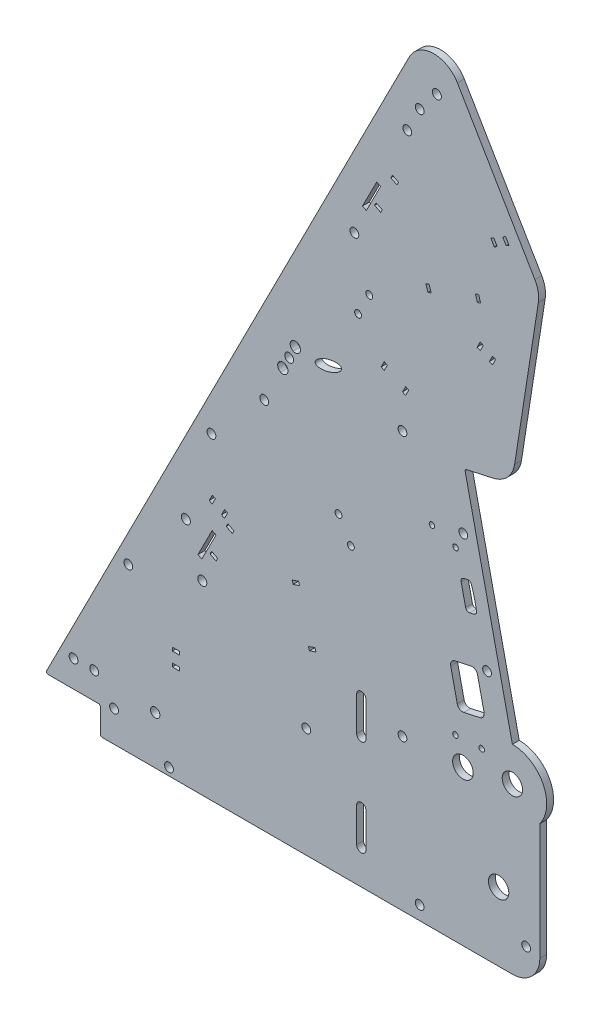
SolidWorks part; units mm, degrees
other "Markup1"
sketch "Sketch5"
ref_plane "Front Plane" through (0, 0, 0) normal (0, 0, 1) x (1, 0, 0)
ref_plane "Top Plane" through (0, 0, 0) normal (0, 1, 0) x (1, 0, 0)
ref_plane "Right Plane" through (0, 0, 0) normal (1, 0, 0) x (0, 0, -1)
sketch "Sketch1" plane through (0, 0, 0) normal (0, 0, 1) x (1, 0, 0)
  line L1 (228.6, -12.7) -> (228.6, 53.975)
  line L2 (178.7547, 351.4131) -> (0, 0)
  line L3 (228.6, 266.7) -> (178.7547, 351.4131)
  line L5 (0, 0) -> (25.4, 0)
  line L6 (25.4, 0) -> (25.4, -12.7)
  line L7 (25.4, -12.7) -> (228.6, -12.7)
  line L9 (215.9, 79.375) -> (193.9097, 178.5667)
  line L10 (193.9097, 178.5667) -> (215.6079, 183.377)
  line L11 (215.6079, 183.377) -> (228.6, 266.7)
  arc A0 (228.6, 53.975) -> (215.9, 79.375) centre (215.9, 63.5) ccw
  dimension "D7" = 12.7
  dimension "D8" = 76.2
  dimension "D10" = 31.75
  dimension "D2" = 279.4
  dimension "D3" = 25.4
  dimension "D4" = 215.9
  dimension "D5" = 394.2644
  dimension "D6" = 203.2
  dimension "D9" = 63.039
  dimension "D11" = 101.6
  dimension "D12" = 12.5
  dimension "D13" = 22.225
extrude "Boss-Extrude1" add sketch "Sketch1" along normal blind 3.175
sketch "Sketch2" plane through (0, 0, 3.175) normal (0, 0, 1) x (1, 0, 0)
  line L0 (178.7547, 351.4131) -> (0, 0) construction
  line L1 (25.4, -12.7) -> (228.6, -12.7) construction
  line L2 (215.9, 79.375) -> (193.9097, 178.5667) construction
  line L3 (193.9097, 178.5667) -> (215.6079, 183.377) construction
  line L4 (215.9, 79.375) -> (193.9097, 178.5667) construction
  line L5 (64.9432, 94.0578) -> (72.5445, 73.1732) construction
  line L6 (64.9432, 94.0578) -> (89.8317, 94.0578) construction
  line L10 (228.6, -12.7) -> (228.6, 53.975) construction
  circle A0 centre (64.9432, 94.0578) radius 2.0955
  circle A1 centre (180.975, 322.1643) radius 2.0955
  circle A2 centre (72.5445, 73.1732) radius 2.0955
  circle A3 centre (193.2078, 152.3944) radius 2.032
  circle A4 centre (215.9, 63.5) radius 4.699
  circle A7 centre (173.0375, -6.35) radius 2.032
  circle A8 centre (204.203, 102.7985) radius 2.032
  circle A26 centre (209.55, 19.05) radius 4.699
  arc A30 (228.6, 53.975) -> (215.9, 79.375) centre (215.9, 63.5) ccw construction
  circle A31 centre (165.1, 179.3875) radius 2.032
  dimension "D3" = 4.191
  dimension "D5" = 4.191
  dimension "D9" = 4.191
  dimension "D20" = 9.398
  dimension "D23" = 9.398
  dimension "D18" = 4.064
  dimension "D26" = 4.064
  dimension "D14" = 4.064
  dimension "D2" = 15.24
  dimension "D6" = 15.24
  dimension "D7" = 22.225
  dimension "D21" = 44.45
  dimension "D22" = 6.35
  dimension "D19" = 160.3375
  dimension "D24" = 44.45
  dimension "D25" = 6.35
  dimension "D27" = 25.4
  dimension "D28" = 50.8
  dimension "D29" = 6.35
  dimension "D17" = 6.35
  dimension "D33" = 55.5625
  dimension "D15" = 114.3
  dimension "D4" = 180.975
  dimension "D8" = 70
extrude "Cut-Extrude1" cut sketch "Sketch2" against normal through all
sketch "Sketch7" plane through (0, 0, 3.175) normal (0, 0, 1) x (1, 0, 0)
  line L0 (146.05, 3.175) -> (146.05, 19.05) construction
  line L1 (143.891, 3.175) -> (143.891, 19.05)
  line L2 (148.209, 3.175) -> (148.209, 19.05)
  line L3 (146.05, 47.625) -> (146.05, 63.5) construction
  line L4 (143.891, 47.625) -> (143.891, 63.5)
  line L5 (148.209, 47.625) -> (148.209, 63.5)
  line L6 (25.4, -12.7) -> (228.6, -12.7) construction
  line L12 (228.6, -12.7) -> (228.6, 53.975) construction
  line L13 (25.4, -12.7) -> (228.6, -12.7) construction
  arc A0 (143.891, 3.175) -> (148.209, 3.175) centre (146.05, 3.175) ccw
  arc A1 (148.209, 19.05) -> (143.891, 19.05) centre (146.05, 19.05) ccw
  arc A2 (143.891, 47.625) -> (148.209, 47.625) centre (146.05, 47.625) ccw
  arc A3 (148.209, 63.5) -> (143.891, 63.5) centre (146.05, 63.5) ccw
  circle A8 centre (50.8, 9.525) radius 2.159
  point P2 (146.05, 11.1125)
  point P9 (146.05, 55.5625)
  dimension "D1" = 4.318
  dimension "D5" = 4.318
  dimension "D2" = 15.875
  dimension "D3" = 15.875
  dimension "D4" = 44.45
  dimension "D6" = 95.25
  dimension "D7" = 82.55
  dimension "D8" = 15.875
  dimension "D9" = 22.225
extrude "Cut-Extrude2" cut sketch "Sketch7" against normal through all
sketch "Sketch10" plane through (0, 0, 3.175) normal (0, 0, 1) x (1, 0, 0)
  circle A1 centre (165.1, 57.15) radius 2.032
  circle A2 centre (120.65, 38.1) radius 2.032
  circle A3 centre (13.0465, 12.3347) radius 2.032
  circle A4 centre (22.5715, 12.3347) radius 2.032
  circle A5 centre (38.3604, 62.564) radius 2.032
  dimension "D1" = 4.064
  dimension "D2" = 4.064
  dimension "D4" = 63.5
  dimension "D5" = 69.85
extrude "Cut-Extrude3" cut sketch "Sketch10" against normal up to next
fillet "Fillet1" radius 12.7 4 edges at (228.6, -12.7, 1.5875) (178.7547, 351.4131, 1.5875) (215.6079, 183.377, 1.5875) (228.6, 266.7, 1.5875)
fillet "Fillet2" radius 0.7937 4 edges at (25.4, -12.7, 1.5875) (25.4, 0, 1.5875) (193.9097, 178.5667, 1.5875) (0, 0, 1.5875)
sketch "Sketch12" plane through (0, 0, 3.175) normal (0, 0, 1) x (1, 0, 0)
  circle A0 centre (31.75, 1.5875) radius 2.032
  circle A1 centre (222.25, 1.5875) radius 2.032
  circle A2 centre (57.15, -9.2075) radius 2.032
  circle A3 centre (57.15, -9.2075) radius 2.286 construction
  dimension "D1" = 4.064
  dimension "D2" = 4.064
extrude "Cut-Extrude5" cut sketch "Sketch12" against normal through all
sketch "Sketch13" plane through (0, 0, 3.175) normal (0, 0, 1) x (1, 0, 0)
  line L2 (194.6847, 178.7385) -> (207.144, 181.5006) construction
  line L5 (199.2434, 101.699) -> (189.6226, 145.0954) construction
  line L6 (189.6022, 69.9806) -> (201.7089, 70.5092) construction
  line L7 (186.8444, 98.9502) -> (199.2434, 101.699)
  line L8 (186.8444, 98.9502) -> (190.9676, 80.3518)
  line L9 (190.9676, 80.3518) -> (203.3665, 83.1006)
  line L10 (199.2434, 101.699) -> (203.3665, 83.1006)
  line L11 (189.6022, 69.9806) -> (190.9676, 80.3518) construction
  line L12 (201.7089, 70.5092) -> (203.3665, 83.1006) construction
  line L13 (215.9, 79.375) -> (194.0815, 177.7917) construction
  line L14 (178.7216, 148.5324) -> (189.6226, 145.0954) construction
  line L15 (195.1281, 134.9336) -> (193.4153, 134.5539)
  line L16 (192.209, 132.6604) -> (194.2706, 123.3612)
  line L17 (196.1641, 122.1549) -> (198.1091, 122.5861)
  line L18 (211.4332, 99.5233) -> (205.2337, 98.1489) construction
  line L19 (198.3765, 158.4184) -> (211.4332, 99.5233) construction
  circle A0 centre (189.6022, 69.9806) radius 1.27
  circle A1 centre (201.7089, 70.5092) radius 1.27
  circle A2 centre (178.7216, 148.5324) radius 1.27
  circle A3 centre (189.6226, 145.0954) radius 1.27
  arc A4 (199.3306, 124.402) -> (196.9796, 133.88) centre (134.9024, 113.4517) ccw
  arc A6 (199.4957, 103.5221) -> (189.2475, 149.7492) centre (134.9024, 113.4517) ccw construction
  arc A7 (195.1281, 134.9336) -> (196.9796, 133.88) centre (195.4717, 133.3837) cw
  arc A8 (198.1091, 122.5861) -> (199.3306, 124.402) centre (197.7655, 124.136) ccw
  arc A9 (194.2706, 123.3612) -> (196.1641, 122.1549) centre (195.8205, 123.7048) ccw
  arc A10 (193.4153, 134.5539) -> (192.209, 132.6604) centre (193.7589, 133.004) ccw
  point P26 (208.3335, 98.8361)
  point P31 (196.515, 135.2411)
  point P36 (194.6142, 121.8113)
  point P39 (191.8654, 134.2103)
  dimension "D7" = 2.54
  dimension "D16" = 1.5875
  dimension "D2" = 11.43
  dimension "D3" = 76.2
  dimension "D4" = 12.7
  dimension "D5" = 19.05
  dimension "D6" = 120
  dimension "D8" = 110
  dimension "D9" = 80
  dimension "D10" = 12.7
  dimension "D11" = 44.45
  dimension "D12" = 11.43
  dimension "D13" = 12.7
  dimension "D14" = 4.7625
  dimension "D15" = 38.1
extrude "Cut-Extrude6" cut sketch "Sketch13" against normal through all both and the other way through all
sketch "Sketch14" plane through (0, 0, 3.175) normal (0, 0, 1) x (1, 0, 0)
  line L0 (26.1937, -12.7) -> (215.9, -12.7) construction
  line L1 (228.6, 0) -> (228.6, 53.975) construction
  line L2 (112.7125, 182.5625) -> (101.1964, 159.9231) construction
  line L3 (168.2448, 330.7518) -> (0.5868, 1.1536) construction
  line L4 (112.7125, 182.5625) -> (136.864, 190.4279) construction
  line L5 (146.6223, 260.2327) -> (153.1864, 273.1371)
  line L6 (146.6223, 260.2327) -> (148.4049, 259.3259)
  line L7 (153.1864, 273.1371) -> (154.969, 272.2304)
  line L8 (148.4049, 259.3259) -> (154.969, 272.2304)
  line L9 (168.2448, 330.7518) -> (0.5868, 1.1536) construction
  line L10 (159.73, 278.0885) -> (160.4498, 279.5035)
  line L11 (159.73, 278.0885) -> (162.5599, 276.649)
  line L12 (160.4498, 279.5035) -> (163.2797, 278.0639)
  line L13 (162.5599, 276.649) -> (163.2797, 278.0639)
  line L14 (152.9292, 264.7188) -> (155.7591, 263.2793)
  line L15 (152.9292, 264.7188) -> (152.2094, 263.3038)
  line L16 (155.7591, 263.2793) -> (155.0394, 261.8643)
  line L17 (152.2094, 263.3038) -> (155.0394, 261.8643)
  line L19 (177.4093, 244.3006) -> (178.3799, 241.2777)
  line L20 (177.4093, 244.3006) -> (175.8978, 243.8153)
  line L21 (178.3799, 241.2777) -> (176.8684, 240.7923)
  line L22 (175.8978, 243.8153) -> (176.8684, 240.7923)
  line L24 (199.7492, 248.1392) -> (198.7785, 251.1622)
  line L25 (199.7492, 248.1392) -> (201.2607, 248.6245)
  line L26 (198.7785, 251.1622) -> (200.29, 251.6475)
  line L27 (201.2607, 248.6245) -> (200.29, 251.6475)
  line L34 (77.0929, 95.5339) -> (78.8755, 94.6271)
  line L47 (77.0929, 95.5339) -> (70.5287, 82.6295)
  line L56 (78.8755, 94.6271) -> (72.3114, 81.7227)
  line L57 (70.5287, 82.6295) -> (72.3114, 81.7227)
  line L58 (84.3562, 101.9002) -> (83.6365, 100.4853)
  line L59 (84.3562, 101.9002) -> (87.1862, 100.4607)
  line L60 (83.6365, 100.4853) -> (86.4664, 99.0458)
  line L61 (87.1862, 100.4607) -> (86.4664, 99.0458)
  line L62 (156.643, 199.3999) -> (158.0826, 202.2298)
  line L63 (156.643, 199.3999) -> (155.2281, 200.1197)
  line L64 (158.0826, 202.2298) -> (156.6676, 202.9496)
  line L65 (155.2281, 200.1197) -> (156.6676, 202.9496)
  line L66 (165.1328, 195.0814) -> (166.5723, 197.9113)
  line L67 (165.1328, 195.0814) -> (166.5478, 194.3617)
  line L68 (166.5723, 197.9113) -> (167.9873, 197.1916)
  line L69 (166.5478, 194.3617) -> (167.9873, 197.1916)
  line L78 (76.8357, 87.1156) -> (76.1159, 85.7006)
  line L79 (201.0549, 233.0581) -> (199.6154, 230.2282)
  line L80 (201.0549, 233.0581) -> (202.4699, 232.3383)
  line L81 (199.6154, 230.2282) -> (201.0304, 229.5084)
  line L82 (202.4699, 232.3383) -> (201.0304, 229.5084)
  line L83 (205.2752, 227.3491) -> (206.7147, 230.1791)
  line L84 (205.2752, 227.3491) -> (206.6902, 226.6294)
  line L85 (206.7147, 230.1791) -> (208.1297, 229.4593)
  line L86 (206.6902, 226.6294) -> (208.1297, 229.4593)
  line L88 (205.9335, 277.0488) -> (207.5436, 274.3124)
  line L89 (205.9335, 277.0488) -> (207.3017, 277.8539)
  line L90 (207.5436, 274.3124) -> (208.9118, 275.1174)
  line L91 (207.3017, 277.8539) -> (208.9118, 275.1174)
  line L92 (211.4063, 280.2691) -> (213.0165, 277.5326)
  line L93 (211.4063, 280.2691) -> (212.7746, 281.0741)
  line L94 (213.0165, 277.5326) -> (214.3847, 278.3377)
  line L95 (212.7746, 281.0741) -> (214.3847, 278.3377)
  line L96 (226.2981, 270.6122) -> (190.5103, 331.4342) construction
  line L97 (76.8357, 87.1156) -> (79.6656, 85.6761)
  line L98 (76.1159, 85.7006) -> (78.9458, 84.2611)
  line L99 (79.6656, 85.6761) -> (78.9458, 84.2611)
  line L100 (121.5929, 71.4121) -> (122.0907, 69.9047)
  line L101 (121.5929, 71.4121) -> (124.6078, 72.4077)
  line L102 (122.0907, 69.9047) -> (125.1056, 70.9003)
  line L103 (124.6078, 72.4077) -> (125.1056, 70.9003)
  line L104 (114.0568, 94.2312) -> (114.5547, 92.7238)
  line L105 (114.0568, 94.2312) -> (117.0717, 95.2269)
  line L106 (114.5547, 92.7238) -> (117.5695, 93.7194)
  line L107 (117.0717, 95.2269) -> (117.5695, 93.7194)
  line L108 (72.4733, 86.4522) -> (77.0385, 95.4269) construction
  line L109 (74.2559, 85.5455) -> (78.8211, 94.5202) construction
  line L110 (75.4207, 87.8353) -> (85.6708, 82.6214) construction
  line L111 (82.2215, 101.205) -> (92.4716, 95.9911) construction
  line L112 (121.0735, 70.3909) -> (122.615, 73.4214) construction
  line L113 (127.0566, 71.1621) -> (122.615, 73.4214) construction
  line L114 (111.5148, 81.8165) -> (118.6783, 95.8993) construction
  line L115 (111.2887, 94.3851) -> (116.5474, 91.7101) construction
  line L116 (148.1447, 263.2257) -> (146.6939, 260.3735) construction
  line L117 (149.9274, 262.319) -> (150.3494, 263.1487) construction
  line L118 (161.7643, 260.2246) -> (151.5142, 265.4385) construction
  line L119 (168.5651, 273.5943) -> (158.315, 278.8082) construction
  line L120 (198.5272, 250.6681) -> (199.2979, 252.1833) construction
  line L121 (197.7564, 249.1529) -> (202.198, 246.8935) construction
  line L122 (202.4094, 246.2251) -> (194.4462, 230.5704) construction
  line L123 (179.402, 243.287) -> (174.1433, 245.962) construction
  line L124 (177.2711, 239.0978) -> (184.4346, 253.1806) construction
  line L125 (189.9159, 224.4756) -> (184.6571, 227.1506) construction
  line L126 (58.7375, 39.6875) -> (61.9125, 39.6875)
  line L127 (58.7375, 39.6875) -> (58.7375, 38.1)
  line L128 (61.9125, 39.6875) -> (61.9125, 38.1)
  line L129 (58.7375, 38.1) -> (61.9125, 38.1)
  line L130 (58.7375, 33.3375) -> (61.9125, 33.3375)
  line L131 (58.7375, 33.3375) -> (58.7375, 31.75)
  line L132 (61.9125, 33.3375) -> (61.9125, 31.75)
  line L133 (58.7375, 31.75) -> (61.9125, 31.75)
  line L135 (77.1911, 109.7326) -> (75.7516, 106.9027)
  line L136 (77.1911, 109.7326) -> (78.606, 109.0128)
  line L137 (75.7516, 106.9027) -> (77.1665, 106.1829)
  line L138 (78.606, 109.0128) -> (77.1665, 106.1829)
  line L139 (81.4114, 104.0237) -> (82.8509, 106.8536)
  line L140 (81.4114, 104.0237) -> (82.8264, 103.3039)
  line L141 (82.8509, 106.8536) -> (84.2659, 106.1338)
  line L142 (82.8264, 103.3039) -> (84.2659, 106.1338)
  circle A0 centre (142.875, 247.65) radius 2.032
  circle A1 centre (112.7125, 182.5625) radius 2.032
  circle A2 centre (101.1964, 159.9231) radius 2.032
  circle A3 centre (149.7335, 226.2069) radius 1.6 construction
  circle A4 centre (144.5649, 216.046) radius 1.6 construction
  circle A5 centre (135.5457, 131.3585) radius 1.6 construction
  circle A6 centre (141.2457, 121.4859) radius 1.6 construction
  circle A7 centre (149.7335, 226.2069) radius 1.6
  circle A8 centre (144.5649, 216.046) radius 1.6
  circle A9 centre (135.5457, 131.3585) radius 1.6
  circle A10 centre (141.2457, 121.4859) radius 1.6
  arc A13 (0, 1.5875) -> (1.5875, 0) centre (1.5875, 1.5875) ccw construction
  ellipse E0 centre (109.8335, 176.9027) end of major axis (108.7539, 174.7802) minor radius 2.32 (108.7539, 174.7802) -> (110.9131, 179.0251) ccw construction
  ellipse E1 centre (109.8335, 176.9027) end of major axis (108.7539, 174.7802) minor radius 2.32 (108.7539, 174.7802) -> (110.9131, 179.0251) ccw
  ellipse E2 centre (130.8261, 188.4615) end of major axis (124.7883, 186.4952) minor radius 2.3812
  ellipse E3 centre (115.5915, 188.2223) end of major axis (114.5119, 186.0999) minor radius 2.32 (114.5119, 186.0999) -> (116.6711, 190.3448) ccw construction
  ellipse E4 centre (115.5915, 188.2223) end of major axis (114.5119, 186.0999) minor radius 2.32 (114.5119, 186.0999) -> (116.6711, 190.3448) ccw
  spline S0 degree 3 poles (1008.5248, 1963.4972) (-264.8214, -935.4578) (153.1817, 166.823) (110.3225, 179.2425) (110.1654, 179.2721) (109.6955, 179.3152) (109.3734, 179.2831) (108.9218, 179.1456) (108.7737, 179.0841) (108.4954, 178.9343) (108.365, 178.8464) (108.1219, 178.6442) (108.0097, 178.5297) (107.8134, 178.2839) (107.7278, 178.1512) (107.5834, 177.8672) (107.527, 177.7202) (107.4441, 177.4168) (107.4178, 177.2585) (107.3978, 176.9432) (107.4036, 176.7863) (107.4465, 176.4736) (107.4841, 176.3175) (107.5874, 176.0205) (107.6532, 175.8777) (107.8133, 175.6037) (107.9066, 175.4748) (116.556, 165.6387) (207.2632, 219.9049) (-1299.313, 1592.6452) knots -17.496982 -17.496982 -17.496982 -17.496982 0.0625 0.0625 0.125 0.125 0.25 0.25 0.3125 0.3125 0.375 0.375 0.4375 0.4375 0.5 0.5 0.5625 0.5625 0.625 0.625 0.6875 0.6875 0.75 0.75 0.8125 0.8125 0.875 0.875 6.02447 6.02447 6.02447 6.02447 only from (110.9131, 179.0251) to (108.7539, 174.7802) construction
  spline S1 degree 3 poles (110.9131, 179.0251) (110.7727, 179.0965) (110.6265, 179.1544) (110.3225, 179.2425) (110.1654, 179.2721) (109.6955, 179.3152) (109.3734, 179.2831) (108.9218, 179.1456) (108.7737, 179.0841) (108.4954, 178.9343) (108.365, 178.8464) (108.1219, 178.6442) (108.0097, 178.5297) (107.8134, 178.2839) (107.7278, 178.1512) (107.5834, 177.8672) (107.527, 177.7202) (107.4441, 177.4168) (107.4178, 177.2585) (107.3978, 176.9432) (107.4036, 176.7863) (107.4465, 176.4736) (107.4841, 176.3175) (107.5874, 176.0205) (107.6532, 175.8777) (107.8133, 175.6037) (107.9066, 175.4748) (108.2178, 175.121) (108.4736, 174.9228) (108.7539, 174.7802) knots 0 0 0 0 0.0625 0.0625 0.125 0.125 0.25 0.25 0.3125 0.3125 0.375 0.375 0.4375 0.4375 0.5 0.5 0.5625 0.5625 0.625 0.625 0.6875 0.6875 0.75 0.75 0.8125 0.8125 0.875 0.875 1 1 1 1
  spline S2 degree 3 poles (-1420.3275, 1467.1358) (182.122, 221.9776) (122.5576, 179.7991) (113.9875, 186.4501) (113.8729, 186.5577) (113.5583, 186.9155) (113.3974, 187.1901) (113.2413, 187.6401) (113.2046, 187.793) (113.1618, 188.1044) (113.1558, 188.2648) (113.176, 188.5797) (113.2018, 188.7347) (113.2848, 189.0394) (113.3426, 189.1891) (113.5563, 189.6095) (113.7586, 189.8627) (114.1212, 190.1647) (114.2542, 190.2544) (114.5324, 190.4041) (114.6775, 190.4645) (114.9798, 190.5567) (115.1369, 190.5882) (115.4499, 190.6199) (115.6074, 190.6207) (115.9244, 190.5918) (116.0795, 190.5623) (127.2954, 187.3224) (125.1094, 104.0575) (-1840.7764, 595.1392) knots -4.189038 -4.189038 -4.189038 -4.189038 0.0625 0.0625 0.125 0.125 0.25 0.25 0.3125 0.3125 0.375 0.375 0.4375 0.4375 0.5 0.5 0.625 0.625 0.6875 0.6875 0.75 0.75 0.8125 0.8125 0.875 0.875 0.9375 0.9375 5.517452 5.517452 5.517452 5.517452 only from (114.5119, 186.0999) to (116.6711, 190.3448) construction
  spline S3 degree 3 poles (114.5119, 186.0999) (114.3711, 186.1715) (114.2359, 186.2574) (113.9875, 186.4501) (113.8729, 186.5577) (113.5583, 186.9155) (113.3974, 187.1901) (113.2413, 187.6401) (113.2046, 187.793) (113.1618, 188.1044) (113.1558, 188.2648) (113.176, 188.5797) (113.2018, 188.7347) (113.2848, 189.0394) (113.3426, 189.1891) (113.5563, 189.6095) (113.7586, 189.8627) (114.1212, 190.1647) (114.2542, 190.2544) (114.5324, 190.4041) (114.6775, 190.4645) (114.9798, 190.5567) (115.1369, 190.5882) (115.4499, 190.6199) (115.6074, 190.6207) (115.9244, 190.5918) (116.0795, 190.5623) (116.3815, 190.4751) (116.53, 190.4166) (116.6711, 190.3448) knots 0 0 0 0 0.0625 0.0625 0.125 0.125 0.25 0.25 0.3125 0.3125 0.375 0.375 0.4375 0.4375 0.5 0.5 0.625 0.625 0.6875 0.6875 0.75 0.75 0.8125 0.8125 0.875 0.875 0.9375 0.9375 1 1 1 1
  point P179 (82.1189, 103.6638)
  dimension "D1" = 4.064
  dimension "D15" = 3.175
  dimension "D2" = 195.2625
  dimension "D3" = 115.8875
  dimension "D4" = 85.725
  dimension "D5" = 260.35
  dimension "D6" = 25.4
  dimension "D7" = 4.7625
  dimension "D8" = 12.7
  dimension "D9" = 19.05
  dimension "D10" = 45
  dimension "D11" = 6.858
  dimension "D12" = 7.62
  dimension "D13" = 3.175
  dimension "D14" = 1.5875
  dimension "D16" = 1.5875
  dimension "D17" = 1.5875
  dimension "D18" = 9.525
  dimension "D19" = 47.625
  dimension "D20" = 38.1
  dimension "D21" = 6.858
  dimension "D22" = 7.62
  dimension "D23" = 1.5875
  dimension "D24" = 3.175
  dimension "D25" = 1.5875
  dimension "D26" = 4.7625
  dimension "D27" = 4.7625
  dimension "D28" = 1.5875
  dimension "D29" = 3.175
  dimension "D30" = 9.525
  dimension "D31" = 4.7625
  dimension "D32" = 4.7625
  dimension "D33" = 1.5875
  dimension "D34" = 3.175
  dimension "D35" = 6.35
  dimension "D36" = 12.7
  dimension "D37" = 1.5875
  dimension "D38" = 3.175
  dimension "D39" = 9.525
  dimension "D40" = 57.15
  dimension "D41" = 44.45
  dimension "D42" = 1.5875
  dimension "D43" = 4.7625
  dimension "D44" = 3.175
extrude "Cut-Extrude7" cut sketch "Sketch14" against normal through all
sketch "Sketch15" plane through (0, 0, 3.175) normal (0, 0, 1) x (1, 0, 0)
  line L0 (168.2448, 330.7518) -> (0.5868, 1.1536) construction
  circle A0 centre (76.7868, 134.1481) radius 2.032
  circle A1 centre (173.0867, 312.2591) radius 2.032
  circle A2 centre (167.3287, 300.9394) radius 2.032
  circle A3 centre (173.0867, 312.2591) radius 1.905 construction
  circle A4 centre (167.3287, 300.9394) radius 1.905 construction
  dimension "D1" = 4.064
  dimension "D4" = 4.064
  dimension "D2" = 7.62
  dimension "D3" = 76.2
extrude "Cut-Extrude8" cut sketch "Sketch15" against normal through all
fillet "Fillet3" radius 2.54 4 edges at (199.2434, 101.699, 1.5875) (186.8444, 98.9502, 1.5875) (190.9676, 80.3518, 1.5875) (203.3665, 83.1006, 1.5875)
sketch "Sketch16" plane through (0, 0, 3.175) normal (0, 0, 1) x (1, 0, 0)
  line L0 (228.6, 0) -> (228.6, 53.975) construction
  line L1 (26.1937, -12.7) -> (215.9, -12.7) construction
  circle A0 centre (193.04, 58.801) radius 4.7625
  dimension "D1" = 9.525
  dimension "D2" = 35.56
  dimension "D3" = 71.501
extrude "Cut-Extrude9" cut sketch "Sketch16" against normal through all
equation "\"D6@Sketch2\"=\"D2@Sketch2\""
